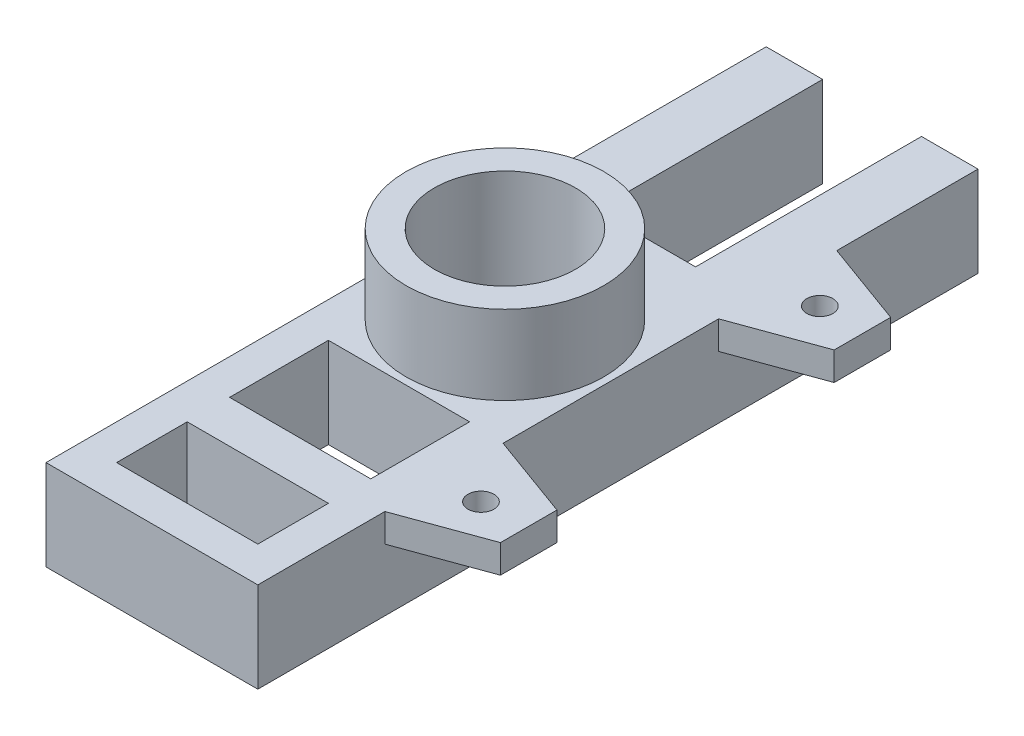
SolidWorks part; units mm, degrees
ref_plane "Front Plane" through (0, 0, 0) normal (0, 0, 1) x (1, 0, 0)
ref_plane "Top Plane" through (0, 0, 0) normal (0, 1, 0) x (1, 0, 0)
ref_plane "Right Plane" through (0, 0, 0) normal (1, 0, 0) x (0, 0, -1)
sketch "Sketch1" plane through (0, 0, 0) normal (0, 1, 0) x (1, 0, 0)
  line L0 (0, 475.2743) -> (0, -355.0119) construction
  line L23 (-47.625, -95.25) -> (-47.625, 63.5)
  line L24 (-86.8798, -194.7602) -> (86.8798, -194.7602) construction
  line L36 (-47.625, 63.5) -> (47.625, 63.5) construction
  line L38 (-31.75, -142.875) -> (31.75, -142.875)
  line L39 (-31.75, -142.875) -> (-31.75, -111.125)
  line L40 (-31.75, -111.125) -> (31.75, -111.125)
  line L41 (31.75, -142.875) -> (31.75, -111.125)
  line L42 (-31.75, -142.875) -> (31.75, -111.125) construction
  line L43 (-31.75, -111.125) -> (31.75, -142.875) construction
  line L44 (-47.625, -158.75) -> (47.625, -158.75)
  line L45 (-47.625, -158.75) -> (-47.625, -95.25)
  line L46 (-47.625, -95.25) -> (47.625, -95.25) construction
  line L47 (47.625, -158.75) -> (47.625, -95.25)
  line L48 (-47.625, -158.75) -> (47.625, -95.25) construction
  line L49 (-47.625, -95.25) -> (47.625, -158.75) construction
  line L50 (47.625, -95.25) -> (47.625, 63.5)
  line L51 (-47.625, 63.5) -> (-47.625, 165.1)
  line L56 (47.625, 63.5) -> (47.625, 165.1)
  line L57 (47.625, 165.1) -> (22.225, 165.1)
  line L58 (22.225, 165.1) -> (22.225, 63.5)
  line L59 (22.225, 63.5) -> (-22.225, 63.5)
  line L60 (-22.225, 63.5) -> (-22.225, 165.1)
  line L61 (-22.225, 165.1) -> (-47.625, 165.1)
  line L63 (-31.75, -47.625) -> (31.75, -47.625)
  line L64 (-31.75, -47.625) -> (-31.75, -92.075)
  line L65 (-31.75, -92.075) -> (31.75, -92.075)
  line L66 (31.75, -47.625) -> (31.75, -92.075)
  line L67 (-31.75, -47.625) -> (31.75, -92.075) construction
  line L68 (-31.75, -92.075) -> (31.75, -47.625) construction
  circle A3 centre (0, 0) radius 31.75
  circle A4 centre (0, 0) radius 44.45
  point P5 (0, -127)
  point P12 (0, -127)
  point P26 (0, -69.85)
  dimension "D1" = 63.5
  dimension "D5" = 88.9
  dimension "D2" = 31.75
  dimension "D3" = 63.5
  dimension "D4" = 127
  dimension "D6" = 63.5
  dimension "D7" = 95.25
  dimension "D8" = 63.5
  dimension "D9" = 25.4
  dimension "D10" = 101.6
  dimension "D11" = 57.15
  dimension "D12" = 44.45
  dimension "D13" = 63.5
extrude "Boss-Extrude1" add sketch "Sketch1" along normal blind 40.64 contours L60 L61 L51 L23 L45 L44 L47 L50 L56 L57 L58 L59 A4 L41 L38 L39 L40 L63 L66 L65 L64 region at (-44.2493, 0, 15.875)
extrude "Boss-Extrude2" add sketch "Sketch1<3>" along normal blind 76.2 contours A4 A3 region at (-43.1928, 0, 0)
sketch "Sketch1<3>" plane through (0, 0, 0) normal (0, 1, 0) x (1, 0, 0) same geometry as "Sketch1"
sketch "Sketch2" plane through (47.625, 0, 0) normal (1, 0, 0) x (0, 0, -1)
  line L0 (0, 0) -> (0, 40.64) construction
  line L1 (-158.75, 40.64) -> (165.1, 40.64) construction
  line L2 (-101.6, 40.64) -> (-101.6, 27.94)
  line L5 (101.6, 27.94) -> (101.6, 40.64)
  line L6 (101.6, 40.64) -> (-101.6, 40.64)
  line L7 (-101.6, 27.94) -> (101.6, 27.94)
  dimension "D1" = 203.2
  dimension "D2" = 101.6
  dimension "D3" = 12.7
extrude "Boss-Extrude3" add sketch "Sketch2" along normal blind 50.8
sketch "Sketch3" plane through (0, 40.64, 0) normal (0, 1, 0) x (1, 0, 0)
  line L0 (0, 0) -> (224.5778, 0) construction
  line L1 (47.625, -101.6) -> (47.625, 101.6) construction
  line L2 (47.625, 101.6) -> (85.725, 87.7327)
  line L4 (85.725, -87.7327) -> (47.625, -101.6)
  line L5 (98.425, -101.6) -> (47.625, -101.6) construction
  line L6 (98.425, 101.6) -> (47.625, 101.6) construction
  line L7 (47.625, 101.6) -> (98.425, 101.6)
  line L8 (98.425, 101.6) -> (98.425, -101.6) construction
  line L9 (98.425, 101.6) -> (98.425, -101.6)
  line L10 (98.425, -101.6) -> (47.625, -101.6)
  line L11 (85.725, 87.7327) -> (85.725, 62.3327)
  line L12 (85.725, 62.3327) -> (47.625, 48.4655)
  line L13 (47.625, 48.4655) -> (47.625, -48.4655)
  line L14 (47.625, -48.4655) -> (85.725, -62.3327)
  line L15 (85.725, -62.3327) -> (85.725, -87.7327)
  circle A0 centre (65.405, 76.2) radius 5.842
  circle A1 centre (65.405, -76.2) radius 5.842
  dimension "D1" = 11.684
  dimension "D2" = 11.684
  dimension "D3" = 17.78
  dimension "D4" = 17.78
  dimension "D5" = 76.2
  dimension "D6" = 76.2
  dimension "D7" = 20
  dimension "D8" = 20
  dimension "D9" = 25.4
  dimension "D10" = 25.4
  dimension "D11" = 38.1
  dimension "D12" = 38.1
  dimension "D13" = 110
extrude "Cut-Extrude1" cut sketch "Sketch3" against normal through all
equation "\"bearingSize\"= 2.5in"
equation "\"D1@Sketch1\"=\"bearingSize\""
